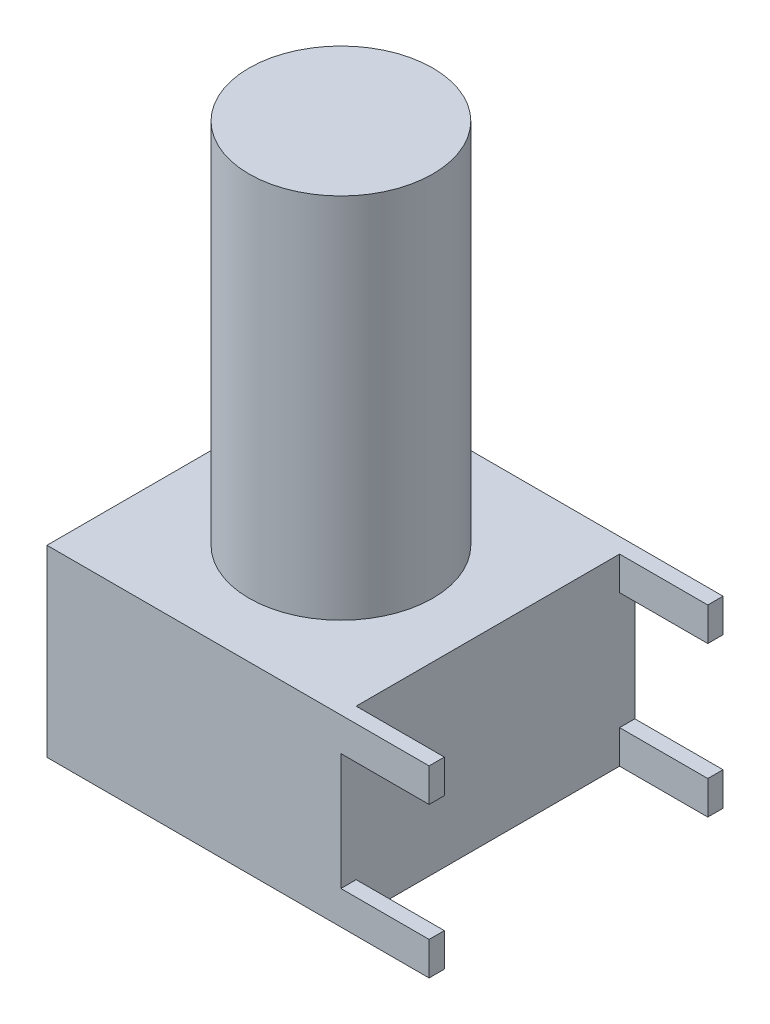
SolidWorks part; units mm, degrees
ref_plane "Front Plane" through (0, 0, 0) normal (0, 0, 1) x (1, 0, 0)
ref_plane "Top Plane" through (0, 0, 0) normal (0, 1, 0) x (1, 0, 0)
ref_plane "Right Plane" through (0, 0, 0) normal (1, 0, 0) x (0, 0, -1)
sketch "Sketch1" plane through (0, 0, 0) normal (0, 1, 0) x (1, 0, 0)
  line L1 (-5.08, -5.08) -> (5.08, -5.08)
  line L2 (-5.08, -5.08) -> (-5.08, 5.08)
  line L3 (-5.08, 5.08) -> (5.08, 5.08)
  line L4 (5.08, -5.08) -> (5.08, 5.08)
  line L5 (-5.08, -5.08) -> (5.08, 5.08) construction
  line L6 (-5.08, 5.08) -> (5.08, -5.08) construction
  circle A0 centre (0, 0) radius 3.175
  point P0 (0, 0)
  dimension "D1" = 6.35
  dimension "D2" = 10.16
  dimension "D3" = 10.16
extrude "Boss-Extrude1" add sketch "Sketch1" along normal blind 12.7 contours A0 region at (0, 0, 0)
extrude "Boss-Extrude2" add sketch "Sketch1<3>" against normal blind 6.35 contours L2 L3 L4 L1
sketch "Sketch1<3>" plane through (0, 0, 0) normal (0, 1, 0) x (1, 0, 0) same geometry as "Sketch1"
sketch "Sketch2" plane through (5.08, 0, 0) normal (1, 0, 0) x (0, 0, -1)
  line L0 (-5.08, -3.175) -> (5.08, -3.175) construction
  line L1 (-5.08, -6.35) -> (-5.08, 0) construction
  line L2 (5.08, -6.35) -> (5.08, 0) construction
  line L3 (0, 0) -> (0, -6.35) construction
  line L4 (-5.08, 0) -> (5.08, 0) construction
  line L5 (-5.08, -6.35) -> (5.08, -6.35) construction
  line L7 (-4.5526, -5.1948) -> (4.5526, -5.1948)
  line L8 (-4.5526, -5.1948) -> (-4.5526, -1.1552)
  line L9 (-4.5526, -1.1552) -> (4.5526, -1.1552)
  line L10 (4.5526, -5.1948) -> (4.5526, -1.1552)
  line L11 (-4.5526, -5.1948) -> (4.5526, -1.1552) construction
  line L12 (-4.5526, -1.1552) -> (4.5526, -5.1948) construction
  line L13 (-5.08, 0) -> (-4.5526, 0)
  line L14 (-5.08, 0) -> (-5.08, -1.1552)
  line L15 (-5.08, -1.1552) -> (-4.5526, -1.1552)
  line L16 (-4.5526, 0) -> (-4.5526, -1.1552)
  line L17 (-5.08, -6.35) -> (-4.5526, -6.35)
  line L18 (-5.08, -6.35) -> (-5.08, -5.1948)
  line L19 (-5.08, -5.1948) -> (-4.5526, -5.1948)
  line L20 (-4.5526, -6.35) -> (-4.5526, -5.1948)
  line L21 (5.08, -6.35) -> (4.5526, -6.35)
  line L22 (5.08, -6.35) -> (5.08, -5.1948)
  line L23 (5.08, -5.1948) -> (4.5526, -5.1948)
  line L24 (4.5526, -6.35) -> (4.5526, -5.1948)
  line L25 (4.5526, -1.1552) -> (5.08, -1.1552)
  line L26 (4.5526, -1.1552) -> (4.5526, 0)
  line L27 (4.5526, 0) -> (5.08, 0)
  line L28 (5.08, -1.1552) -> (5.08, 0)
  point P12 (0, -3.175)
  line M1 (5.08, 0) -> (-5.08, 0)
  line M2 (-5.08, 0) -> (-5.08, -6.35)
  line M3 (-5.08, -6.35) -> (5.08, -6.35)
  line M4 (5.08, -6.35) -> (5.08, 0)
extrude "Boss-Extrude3" add sketch "Sketch2" along normal blind 3.048 contours L16 L15 M1 M2 | L26 L25 M4 M1 | L24 L23 M3 M4 | L20 L19 M3 M2 region at (5.08, -5.7724, 4.8163) region at (5.08, -5.7724, -4.8163) region at (5.08, -0.5776, 4.8163) region at (5.08, -0.5776, -4.8163)
